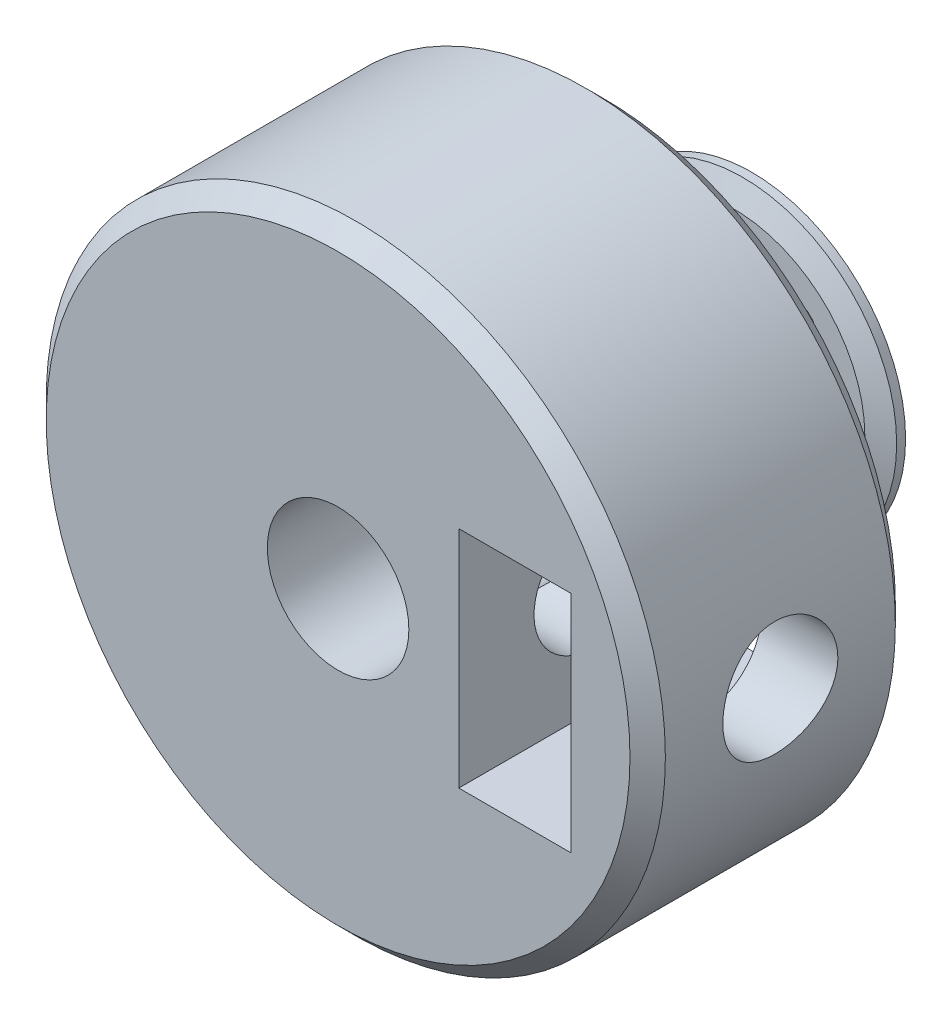
SolidWorks part; units mm, degrees
ref_plane "Front Plane" through (0, 0, 0) normal (0, 0, 1) x (1, 0, 0)
ref_plane "Top Plane" through (0, 0, 0) normal (0, 1, 0) x (1, 0, 0)
ref_plane "Right Plane" through (0, 0, 0) normal (1, 0, 0) x (0, 0, -1)
sketch "Sketch1" plane through (0, 0, 0) normal (0, 0, 1) x (1, 0, 0)
  line L1 (-1.7499, 5.3585) -> (1.7499, 5.3585) construction
  line L4 (0, 0) -> (0, 5.3585) construction
  line L5 (0, 5.3585) -> (0, 11.2111) construction
  line L6 (0, 6.3625) -> (1.9751, 6.0482) construction
  line L7 (1.9751, 6.0482) -> (2.6648, 5.8229) construction
  line L8 (1.9751, 6.0482) -> (1.7499, 5.3585) construction
  line L9 (-1.9751, 6.0482) -> (-1.7499, 5.3585) construction
  line L10 (-1.8963, 5.8067) -> (-2.841, 8.6995)
  line L11 (-2.841, 8.6995) -> (2.841, 8.6995)
  line L12 (2.841, 8.6995) -> (1.8963, 5.8067)
  circle A0 centre (0, 0) radius 6.3625 construction
  circle A1 centre (0, 0) radius 8.6995 construction
  circle A2 centre (0, 0) radius 6.1085 construction
  arc A3 (-0.4989, 5.6703) -> (0.4989, 5.6703) centre (0, 5.9135) ccw
  arc A4 (-0.4989, 5.6703) -> (-0.5855, 5.9387) centre (0.4, 6.1085) cw
  arc A5 (-1.8963, 5.8067) -> (-0.7518, 6.0621) centre (0, 0) cw
  arc A6 (-0.5855, 5.9387) -> (-0.7518, 6.0621) centre (-0.7333, 5.9132) ccw
  arc A7 (1.8963, 5.8067) -> (0.7518, 6.0621) centre (0, 0) ccw
  arc A8 (0.5855, 5.9387) -> (0.7518, 6.0621) centre (0.7333, 5.9132) cw
  arc A9 (0.4989, 5.6703) -> (0.5855, 5.9387) centre (-0.4, 6.1085) ccw
  point P6 (0, 20.9083)
  point P11 (0, 6.3625)
  point P13 (0, 8.6995)
  point P14 (0, 6.1085)
  dimension "D1" = 9.6972
  dimension "D2" = 4.8486
sketch "Sketch2" plane through (0, 0, 0) normal (1, 0, 0) x (0, 0, -1)
  line L0 (-10, 4) -> (10, 4)
  line L1 (-10, 4) -> (-10, 8.6995)
  line L2 (1.115, 8.6995) -> (-10, 8.6995)
  line L3 (0.61, 4) -> (0.61, 8.6995) construction
  line L4 (0.61, 8.6995) -> (1.62, 8.6995) construction
  line L5 (1.62, 8.6995) -> (1.62, 6.1085) construction
  line L6 (1.62, 6.1085) -> (8.99, 6.1085)
  line L7 (8.99, 6.1085) -> (8.99, 8.6995) construction
  line L8 (8.99, 8.6995) -> (10, 8.6995) construction
  line L9 (10, 8.6995) -> (10, 4)
  line L10 (-10, 0) -> (10, 0) construction
  line L11 (9.495, 8.6995) -> (8.99, 7.404)
  line L12 (1.62, 7.404) -> (1.115, 8.6995)
  line L14 (1.62, 7.404) -> (1.62, 6.1085)
  line L15 (8.99, 6.1085) -> (8.99, 7.404)
  line L16 (9.495, 8.6995) -> (10, 8.6995)
  arc A0 (1.62, 7.404) -> (1.115, 8.6995) centre (-0.2942, 7.404) ccw construction
  arc A1 (8.99, 7.404) -> (9.495, 8.6995) centre (10.9042, 7.404) cw construction
  point P12 (1.62, 7.404)
  point P14 (1.115, 8.6995)
  point P20 (8.99, 7.404)
  point P21 (9.495, 8.6995)
  point P25 (8.99, 0)
  point P26 (1.62, 0)
  dimension "OA" = 20
  dimension "Bore" = 8
  dimension "Outside Width" = 8.38
  dimension "Inside Width" = 7.37
revolve "Revolve1" add sketch "Sketch2" angle 360 mid plane about L10
sketch "Sketch3" plane through (0, 0, 0) normal (0, 0, 1) x (1, 0, 0)
  line L6 (2.841, 8.6995) -> (-2.841, 8.6995)
  line L7 (1.8963, 5.8067) -> (2.841, 8.6995)
  line L8 (-2.841, 8.6995) -> (-1.8963, 5.8067)
  line L9 (2.841, 8.6995) -> (-2.841, 8.6995)
  line L10 (1.8963, 5.8067) -> (2.841, 8.6995)
  line L11 (-2.841, 8.6995) -> (-1.8963, 5.8067)
  arc A8 (1.8963, 5.8067) -> (0.7518, 6.0621) centre (0, 0) ccw
  arc A9 (0.7518, 6.0621) -> (0.5855, 5.9387) centre (0.7333, 5.9132) ccw
  arc A10 (0.4989, 5.6703) -> (0.5855, 5.9387) centre (-0.4, 6.1085) ccw
  arc A11 (-0.4989, 5.6703) -> (0.4989, 5.6703) centre (0, 5.9135) ccw
  arc A12 (-0.5855, 5.9387) -> (-0.4989, 5.6703) centre (0.4, 6.1085) ccw
  arc A13 (-0.5855, 5.9387) -> (-0.7518, 6.0621) centre (-0.7333, 5.9132) ccw
  arc A14 (-0.7518, 6.0621) -> (-1.8963, 5.8067) centre (0, 0) ccw
  arc A15 (1.8963, 5.8067) -> (0.7518, 6.0621) centre (0, 0) ccw
  arc A16 (0.7518, 6.0621) -> (0.5855, 5.9387) centre (0.7333, 5.9132) ccw
  arc A17 (0.4989, 5.6703) -> (0.5855, 5.9387) centre (-0.4, 6.1085) ccw
  arc A18 (-0.4989, 5.6703) -> (0.4989, 5.6703) centre (0, 5.9135) ccw
  arc A19 (-0.5855, 5.9387) -> (-0.4989, 5.6703) centre (0.4, 6.1085) ccw
  arc A20 (-0.5855, 5.9387) -> (-0.7518, 6.0621) centre (-0.7333, 5.9132) ccw
  arc A21 (-0.7518, 6.0621) -> (-1.8963, 5.8067) centre (0, 0) ccw
  dimension "D1" = 0
extrude "Cut-Extrude1" cut sketch "Sketch3" against normal up to vertex (8.99 mm away) from vertex up to point (0, 6.1085, -8.99) starting at point (0, 6.1085, -1.62)
pattern_circular "CirPattern1" count 20 over 360 about axis through (0, 0, 10) along (0, 0, 1) of "Cut-Extrude1"
sketch "Sketch4" plane through (0, 0, 0) normal (1, 0, 0) x (0, -1, 0)
  line L0 (0, 1.62) -> (0, -10) construction
  line L1 (-4, -10) -> (4, -10) construction
  line L2 (7.404, 1.62) -> (-7.404, 1.62) construction
  circle A0 centre (0, -4.19) radius 1.7526
extrude "Cut-Extrude2" cut sketch "Sketch4" along normal through all
ref_plane "Plane1" through (0, 0, 4.19) normal (0, 0, 1) x (1, 0, 0)
sketch "Sketch5" plane through (0, 0, 4.19) normal (0, 0, 1) x (1, 0, 0)
  line L0 (0, 0) -> (0, 8.6995) construction
  line L1 (4, -1.3716) -> (4, 0)
  line L2 (4.381, -1.7526) -> (8.1401, -1.7526)
  line L3 (4, 0) -> (8.6995, 0) construction
  line L4 (4, 0) -> (8.5211, 0)
  line L5 (8.5211, 0) -> (8.5211, -1.3716)
  line L6 (4.381, -1.7526) -> (4, -1.3716)
  line L7 (8.5211, -1.3716) -> (8.1401, -1.7526)
  circle A0 centre (0, 0) radius 8.6995 construction
  circle A1 centre (0, 0) radius 4 construction
  point P2 (4, -1.7526)
  point P11 (8.5211, -1.7526)
revolve "Revolve2" add sketch "Sketch5" angle 360 mid plane about L4
sketch "Sketch6" plane through (8.5211, 5.3841, 0) normal (-1, 0, 0) x (0, -1, 0)
  line L1 (5.3841, 5.2019) -> (4.5078, 4.6959)
  line L2 (4.5078, 4.6959) -> (4.5078, 3.6841)
  line L3 (4.5078, 3.6841) -> (5.3841, 3.1781)
  line L4 (5.3841, 3.1781) -> (6.2604, 3.6841)
  line L5 (6.2604, 3.6841) -> (6.2604, 4.6959)
  line L6 (6.2604, 4.6959) -> (5.3841, 5.2019)
  circle A0 centre (5.3841, 4.19) radius 0.8763 construction
  dimension "D1" = 1.7526
extrude "Cut-Extrude3" cut sketch "Sketch6" along normal blind 1.3144
pattern_circular "CirPattern3" count 2 over 90 about axis through (0, 0, 10) along (0, 0, 1) of "Cut-Extrude2", "Revolve2", "Cut-Extrude3"
chamfer "Chamfer1" distance 0.2807 angle 45 2 edges at (4, 0, 10) (8.6995, 0, 10)
ref_axis "Center Axis 1" through (0, 0, -10) along (0, 0, 1)
ref_plane "Contact Plane 1" through (0, 0, 10) normal (0, 0, 1) x (1, 0, 0)
ref_plane "Contact Plane 2" through (0, 0, -10) normal (0, 0, -1) x (-1, 0, 0)
sketch "Sketch7" plane through (0, 0, -1.62) normal (0, 0, 1) x (1, 0, 0)
  circle A2 centre (0, 0) radius 4 construction
  circle A3 centre (0, 0) radius 4
  circle A4 centre (0, 0) radius 17.5
  dimension "D1" = 35
extrude "Boss-Extrude1" add sketch "Sketch7" along normal blind 15
chamfer "Chamfer2" distance 1 angle 45 2 edges at (17.5, 0, -1.62) (17.5, 0, 13.38)
sketch "Sketch8" plane through (0, 0, -1.62) normal (0, 0, 1) x (1, 0, 0)
  line L1 (6.825, 6.35) -> (13.175, 6.35)
  line L2 (6.825, 6.35) -> (6.825, -6.35)
  line L3 (6.825, -6.35) -> (13.175, -6.35)
  line L4 (13.175, 6.35) -> (13.175, -6.35)
  line L5 (6.825, 6.35) -> (13.175, -6.35) construction
  line L6 (6.825, -6.35) -> (13.175, 6.35) construction
  point P4 (10, 0)
  point P5 (0, 0)
  dimension "D1" = 6.35
  dimension "D2" = 12.7
  dimension "D3" = 10
extrude "Cut-Extrude4" cut sketch "Sketch8" along normal through all
sketch "Sketch9" plane through (6.825, 0, 0) normal (1, 0, 0) x (0, 0, -1)
  line L1 (-13.38, 16.5) -> (-13.38, -16.5) construction
  circle A0 centre (-5.88, 0) radius 3.25
  point P2 (0, 0)
  dimension "D1" = 6.5
  dimension "D2" = 7.5
extrude "Cut-Extrude5" cut sketch "Sketch9" against normal up to next and the other way through all
equation "\"D2@Sketch1\"= \"D1@Sketch1\" / 2"
equation "\"D1@Sketch6\" = \"Set Screw@Sketch4\" / 2"
equation "\"D1@Cut-Extrude3\" = \"D1@Sketch6\"*.75"
